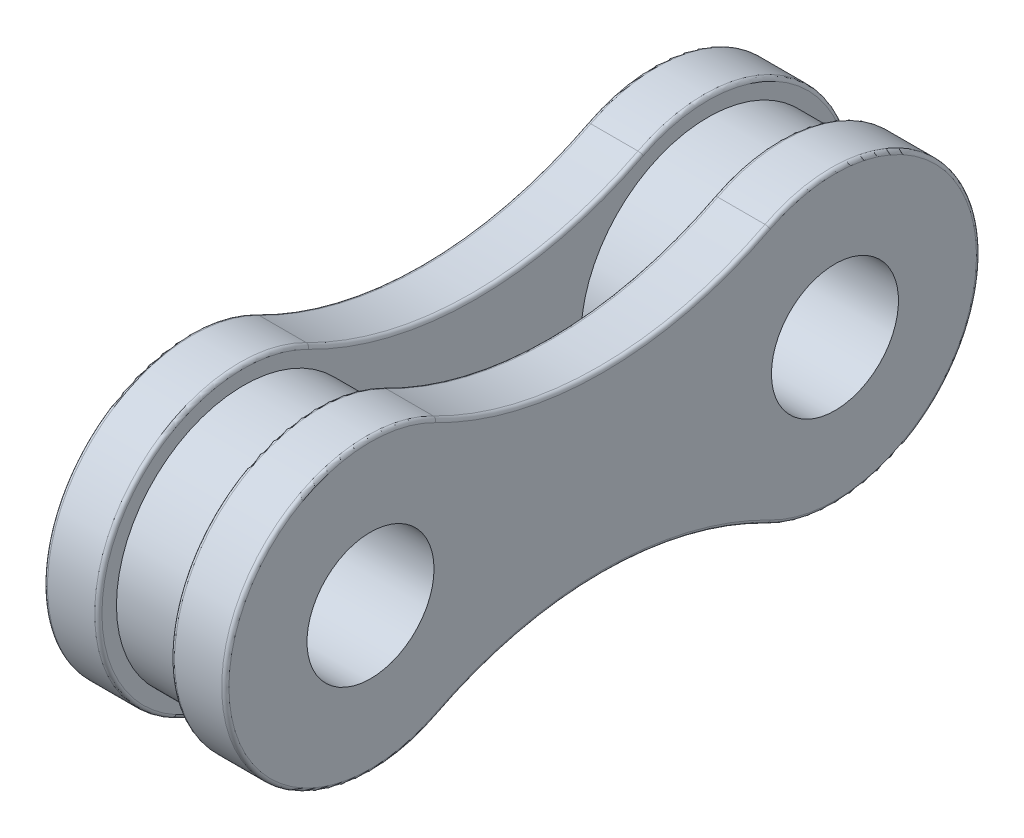
SolidWorks part; units mm, degrees
ref_plane "Front Plane" through (0, 0, 0) normal (0, 0, 1) x (1, 0, 0)
ref_plane "Top Plane" through (0, 0, 0) normal (0, 1, 0) x (1, 0, 0)
ref_plane "Right Plane" through (0, 0, 0) normal (1, 0, 0) x (0, 0, -1)
sketch "Sketch1" plane through (0, 0, 0) normal (1, 0, 0) x (0, 0, -1)
  line L0 (6.3985, 0) -> (-6.3985, 0) construction
  line L1 (0, -12265.2787) -> (0, 12284.0066) construction
  arc A0 (-4.5704, 3.5578) -> (-4.5704, -3.5578) centre (-6.3985, 0) ccw
  circle A1 centre (-6.3985, 0) radius 1.75
  circle A2 centre (6.3985, 0) radius 1.75
  arc A3 (4.5704, 3.5578) -> (4.5704, -3.5578) centre (6.3985, 0) cw
  arc A4 (-4.5704, 3.5578) -> (4.5704, 3.5578) centre (0, 12.4523) ccw
  arc A5 (-4.5704, -3.5578) -> (4.5704, -3.5578) centre (0, -12.4523) cw
  dimension "D2" = 8
  dimension "D3" = 3.5
  dimension "D4" = 10
  dimension "D1" = 12.797
extrude "Boss-Extrude1" add sketch "Sketch1" along normal blind 1.5 from offset 1
sketch "Sketch2" plane through (0, 0, 0) normal (1, 0, 0) x (0, 0, -1)
  circle A0 centre (-6.3985, 0) radius 1.75 construction
  circle A1 centre (6.3985, 0) radius 1.75 construction
  circle A2 centre (-6.3985, 0) radius 1.75
  circle A3 centre (6.3985, 0) radius 1.75
  arc A4 (4.5704, -3.5578) -> (-4.5704, -3.5578) centre (0, -12.4523) ccw
  arc A5 (4.5704, -3.5578) -> (4.5704, 3.5578) centre (6.3985, 0) ccw
  arc A6 (-4.5704, 3.5578) -> (4.5704, 3.5578) centre (0, 12.4523) ccw
  arc A7 (-4.5704, 3.5578) -> (-4.5704, -3.5578) centre (-6.3985, 0) ccw
  arc A8 (4.5704, -3.5578) -> (-4.5704, -3.5578) centre (0, -12.4523) ccw
  arc A9 (4.5704, -3.5578) -> (4.5704, 3.5578) centre (6.3985, 0) ccw
  arc A10 (-4.5704, 3.5578) -> (4.5704, 3.5578) centre (0, 12.4523) ccw
  arc A11 (-4.5704, 3.5578) -> (-4.5704, -3.5578) centre (-6.3985, 0) ccw
  dimension "D1" = 0
extrude "Boss-Extrude2" add sketch "Sketch2" against normal blind 1.5 from offset 1 separate body offset against normal yes
sketch "Sketch3" plane through (0, 0, 0) normal (1, 0, 0) x (0, 0, -1)
  line L0 (0, -1146.9345) -> (0, 5479.7981) construction
  circle A0 centre (6.3985, 0) radius 1.75 construction
  circle A1 centre (-6.3985, 0) radius 1.75 construction
  circle A2 centre (6.3985, 0) radius 1.75
  circle A3 centre (-6.3985, 0) radius 1.75
  circle A4 centre (6.3985, 0) radius 3.5
  circle A5 centre (-6.3985, 0) radius 3.5
  dimension "D1" = 7
extrude "Boss-Extrude3" add sketch "Sketch3" along normal mid plane 2
fillet "Fillet1" radius 0.1 16 edges at (2.5, 0, 10.3985) (2.5, 2.4523, 0) (2.5, 0, -10.3985) (1, 0, 10.3985) (1, 2.4523, 0) (1, 0, -10.3985) (-1, 0, 10.3985) (-1, 2.4523, 0) (-1, 0, -10.3985) (-2.5, 0, 10.3985) (-2.5, 2.4523, 0) (-2.5, 0, -10.3985) (2.5, -2.4523, 0) (1, -2.4523, 0) (-1, -2.4523, 0) (-2.5, -2.4523, 0)
